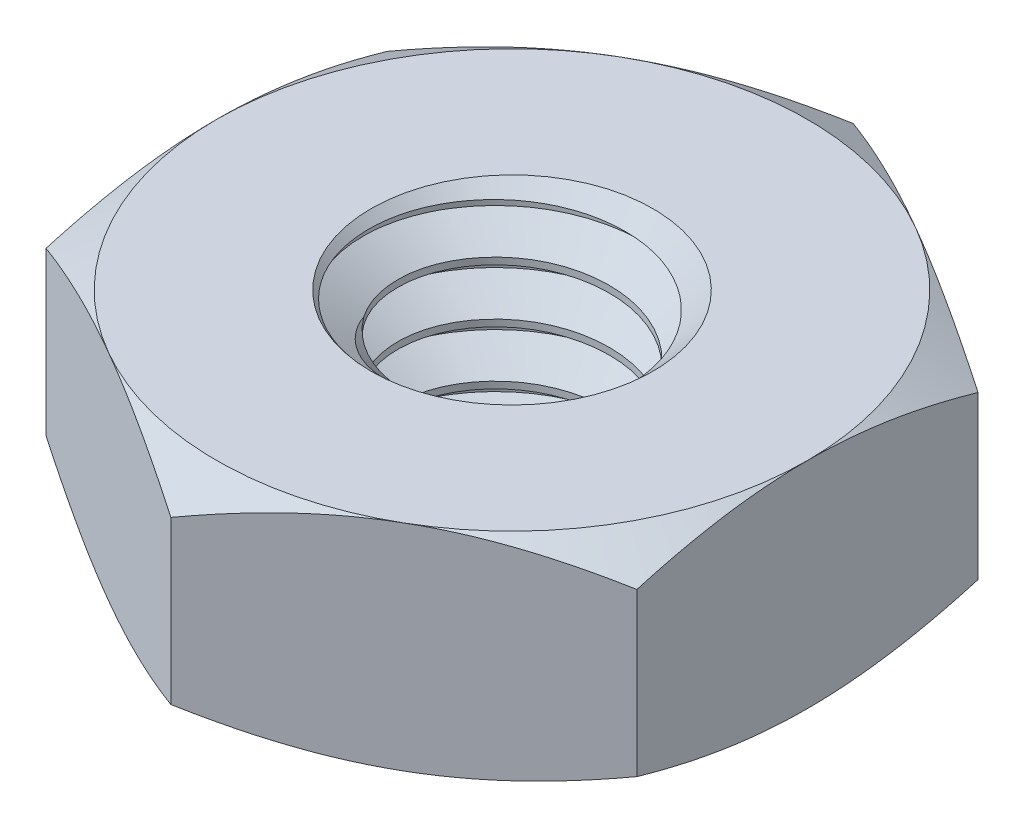
SolidWorks part; units mm, degrees
material "AISI 304"
ref_plane "Front Plane" through (0, 0, 0) normal (0, 0, 1) x (1, 0, 0)
ref_plane "Top Plane" through (0, 0, 0) normal (0, 1, 0) x (1, 0, 0)
ref_plane "Right Plane" through (0, 0, 0) normal (1, 0, 0) x (0, 0, -1)
sketch "Sketch1" plane through (0, 0, 0) normal (0, 1, 0) x (1, 0, 0)
  line L0 (-4.3656, 0) -> (4.3656, 0) construction
  point P0 (0, 0)
  dimension "Width" = 8.7312
sketch "Sketch2" plane through (0, 0, 0) normal (1, 0, 0) x (0, 0, -1)
  line L0 (0, 1.5875) -> (0, -1.5875) construction
  line L1 (-2.0828, 1.5875) -> (2.0828, 1.5875) construction
  line L2 (-2.0828, 1.5875) -> (-2.0828, 0.7937) construction
  point P4 (0, 0)
  point P8 (0, 1.5875)
sketch "Sketch11" plane through (0, 0, 0) normal (0, 1, 0) x (1, 0, 0)
  line L1 (-4.3656, 2.5205) -> (-4.3656, -2.5205)
  line L2 (-4.3656, -2.5205) -> (0, -5.041)
  line L3 (0, -5.041) -> (4.3656, -2.5205)
  line L4 (4.3656, -2.5205) -> (4.3656, 2.5205)
  line L5 (4.3656, 2.5205) -> (0, 5.041)
  line L6 (0, 5.041) -> (-4.3656, 2.5205)
  circle A0 centre (0, 0) radius 4.3656 construction
  circle A1 centre (0, 0) radius 2.0828
extrude "Boss-Extrude1" add sketch "Sketch11" along normal mid plane 3.175
sketch "Sketch5" plane through (0, 1.5875, 0) normal (0, 1, 0) x (1, 0, 0)
  circle A0 centre (0, 0) radius 4.3656 construction
  circle A1 centre (0, 0) radius 4.3656
extrude "Cut-Extrude1" cut sketch "Sketch5" against normal through all draft 60 flip side to cut
mirror "Mirror1" about plane through (0, 0, 0) normal (0, 1, 0) of "Cut-Extrude1"
sketch "Sketch27" plane through (0, 0, 0) normal (0, 1, 0) x (1, 0, 0)
  line L0 (1.4728, -1.4728) -> (-1.4728, 1.4728) construction
  line L2 (0, -2.0828) -> (0, 2.0828) construction
  point P5 (0, 0)
  point P8 (1.4728, -1.4728)
  point P9 (-1.4728, 1.4728)
  dimension "D1" = 45
sketch "Sketch22" plane through (0, 1.5875, 0) normal (0, 1, 0) x (1, 0, 0)
  circle A0 centre (0, 0) radius 2.0828 construction
  circle A1 centre (0, 0) radius 2.0828
curve "Helix/Spiral1" pitch 0.7937 height 3.9688 radius 2.0828 centre (0, 1.5875, 0) axis (0, -1, 0) start towards (0, 0, 1) parameters "Pitch"=0.7937
sketch "Sketch23" plane through (0, 1.5875, 0) normal (0, 1, 0) x (1, 0, 0)
  circle A0 centre (0, 0) radius 2.0828
extrude "Boss-Extrude2" add sketch "Sketch23" against normal up to vertex (3.175 mm away) separate body up to point (0, -1.5875, 0)
sketch "Sketch24" plane through (0, 1.5875, 0) normal (0, 1, 0) x (1, 0, 0)
  line L0 (0, -2.0828) -> (0, 2.0828) construction
  circle A0 centre (0, 0) radius 2.0828
extrude "Boss-Extrude3" add sketch "Sketch24" against normal up to vertex (3.175 mm away) up to point (0, -1.5875, 0)
sketch "Sketch25" plane through (0, 0, 0) normal (1, 0, 0) x (0, 0, -1)
  line L0 (-2.0828, 1.5875) -> (-2.0828, 2.282)
  line L1 (-2.0828, 2.282) -> (-1.5672, 1.9844)
  line L2 (-1.5672, 1.9844) -> (-1.5672, 1.8852)
  line L3 (-1.5672, 1.8852) -> (-2.0828, 1.5875)
  line L4 (-2.0828, 1.9348) -> (-1.5672, 1.9348) construction
  line L5 (-1.825, 1.7363) -> (-1.825, 2.1332) construction
  dimension "D1" = 0.0992
  dimension "D2" = 0.3969
  dimension "D3" = 60
sweep "Cut-Sweep1" cut profiles "Sketch25" path "Helix/Spiral1" align with end faces yes
combine bodies "Combine1" operation type subtract main body 107 bodies to subtract 108
sketch "Sketch26" plane through (0, 1.5875, 0) normal (0, 1, 0) x (1, 0, 0)
  line L0 (-4.3656, 0) -> (4.3656, 0) construction
  circle A0 centre (0, 0) radius 2.0828
extrude "Cut-Extrude2" cut sketch "Sketch26" against normal through all draft 45
mirror "Mirror2" about plane through (0, 0, 0) normal (0, 1, 0) of "Cut-Extrude2"
equation "\"D3@Helix/Spiral1\" = \"Height@Sketch2\" + \"Pitch@Sketch2\""
equation "\"Pitch@Helix/Spiral1\"=\"Pitch@Sketch2\""
equation "\"D1@Sketch25\"=\"Pitch@Sketch2\"*.125"
equation "\"D2@Sketch25\"=\"Pitch@Sketch2\"*.5"
